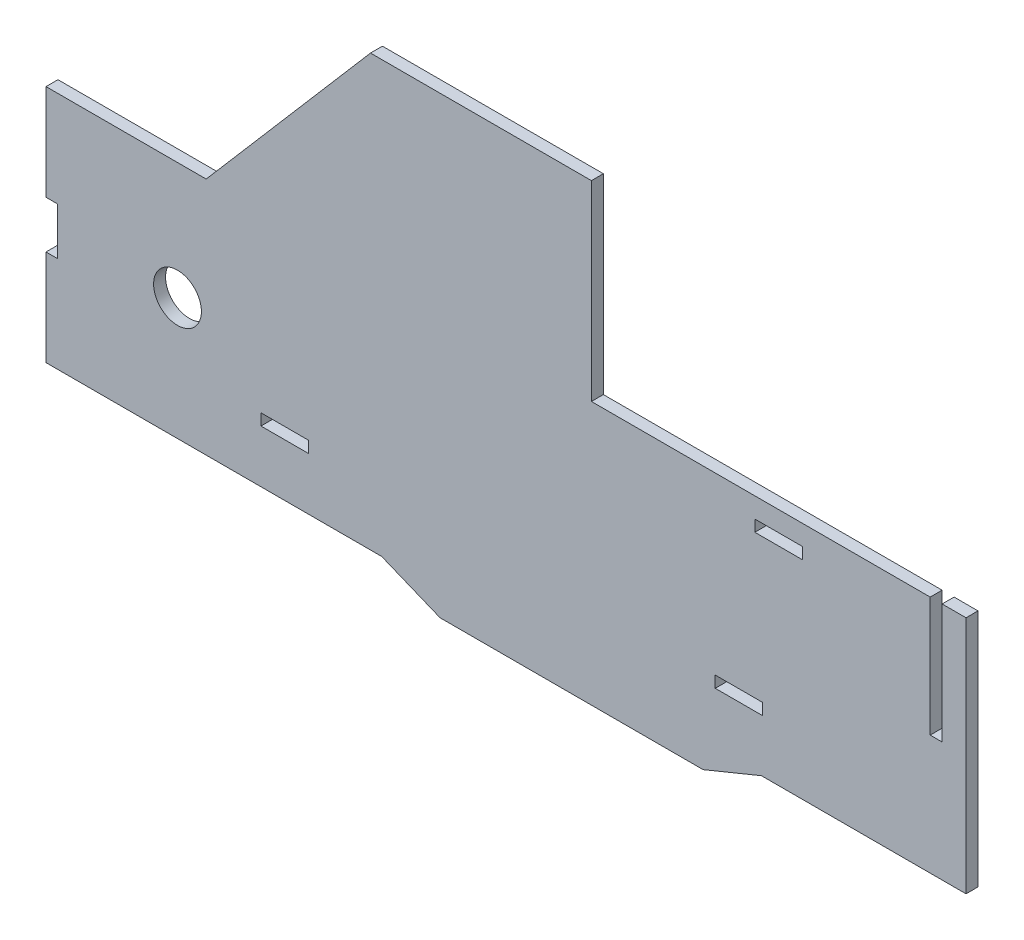
SolidWorks part; units mm, degrees
ref_plane "Front Plane" through (0, 0, 0) normal (0, 0, 1) x (1, 0, 0)
ref_plane "Top Plane" through (0, 0, 0) normal (0, 1, 0) x (1, 0, 0)
ref_plane "Right Plane" through (0, 0, 0) normal (1, 0, 0) x (0, 0, -1)
sketch "Sketch1" plane through (0, 0, 0) normal (0, 0, 1) x (1, 0, 0)
  line L0 (62.1239, 6.35) -> (131.9663, 6.35)
  line L1 (201.8088, 12.7) -> (201.8088, 76.2)
  line L2 (201.8088, 76.2) -> (102.3141, 76.2)
  line L3 (102.3141, 76.2) -> (102.3141, 127)
  line L4 (102.3141, 127) -> (43.6394, 127)
  line L5 (43.6394, 127) -> (0, 76.2)
  line L6 (0, 76.2) -> (-42.5392, 76.2)
  line L7 (-42.5392, 76.2) -> (-42.5392, 12.7)
  line L9 (-42.5392, 12.7) -> (46.6174, 12.7)
  line L10 (46.6174, 12.7) -> (62.1239, 6.35)
  line L11 (201.8088, 12.7) -> (147.4729, 12.7)
  line L12 (147.4729, 12.7) -> (131.9663, 6.35)
  dimension "D1" = 244.348
  dimension "D2" = 6.35
  dimension "D3" = 50.8
  dimension "D4" = 63.5
  dimension "D5" = 99.4947
  dimension "D6" = 16.7564
  dimension "D7" = 16.7564
extrude "Main Side" add sketch "Sketch1" along normal blind 3.175
sketch "Sketch2" plane through (0, 0, 3.175) normal (0, 0, 1) x (1, 0, 0)
  line L0 (-39.4912, 76.2) -> (-39.4912, 12.7) construction
  line L15 (0, 76.2) -> (-42.5392, 76.2) construction
  line L16 (-42.5392, 76.2) -> (-42.5392, 12.7) construction
  line L26 (-39.4912, 18.5744) -> (201.8088, 18.5744) construction
  line L27 (201.8088, 12.7) -> (201.8088, 76.2) construction
  line L28 (81.1588, 18.5744) -> (81.1588, 127) construction
  line L29 (102.3141, 127) -> (43.6394, 127) construction
  line L30 (81.1588, 36.7006) -> (201.8088, 36.7006) construction
  line L41 (62.1239, 6.35) -> (131.9663, 6.35) construction
  line L42 (135.1973, 29.718) -> (147.7703, 29.718)
  line L43 (135.1973, 29.718) -> (135.1973, 26.67)
  line L44 (135.1973, 26.67) -> (147.7703, 26.67)
  line L45 (147.7703, 29.718) -> (147.7703, 26.67)
  line L46 (14.5473, 29.718) -> (14.5473, 26.67)
  line L47 (27.1203, 26.67) -> (14.5473, 26.67)
  line L48 (27.1203, 29.718) -> (27.1203, 26.67)
  line L49 (27.1203, 29.718) -> (14.5473, 29.718)
  line L51 (-42.5392, 12.7) -> (46.6174, 12.7) construction
  point P20 (141.4838, 29.718)
  point P21 (141.4838, 36.7006)
  dimension "D1" = 12.573
  dimension "D2" = 3.048
  dimension "D3" = 20.32
  dimension "D4" = 3.048
extrude "Bottom Plate Holes" cut sketch "Sketch2" against normal through all
sketch "Sketch3" plane through (0, 0, 3.175) normal (0, 0, 1) x (1, 0, 0)
  line L1 (145.7115, 70.866) -> (158.4115, 70.866)
  line L2 (145.7115, 70.866) -> (145.7115, 67.818)
  line L3 (145.7115, 67.818) -> (158.4115, 67.818)
  line L4 (158.4115, 70.866) -> (158.4115, 67.818)
  line L6 (147.7703, 29.718) -> (135.1973, 29.718) construction
  line L7 (201.8088, 76.2) -> (102.3141, 76.2) construction
  point P8 (152.0615, 76.2)
  point P9 (152.0615, 70.866)
  dimension "D1" = 12.7
  dimension "D2" = 3.048
  dimension "D3" = 38.1
extrude "Cut-Extrude1" cut sketch "Sketch3" against normal through all
sketch "Sketch4" plane through (0, 0, 3.175) normal (0, 0, 1) x (1, 0, 0)
  line L0 (-42.5392, 76.2) -> (-42.5392, 12.7) construction
  line L1 (-42.5392, 50.7365) -> (-39.4912, 50.7365)
  line L2 (-42.5392, 50.7365) -> (-42.5392, 38.1635)
  line L3 (-42.5392, 38.1635) -> (-39.4912, 38.1635)
  line L4 (-39.4912, 50.7365) -> (-39.4912, 38.1635)
  point P6 (-42.5392, 44.45)
  point P7 (-42.5392, 44.45)
  dimension "D1" = 3.048
  dimension "D2" = 12.573
extrude "Cut-Extrude2" cut sketch "Sketch4" against normal through all
sketch "Sketch5" plane through (0, 0, 3.175) normal (0, 0, 1) x (1, 0, 0)
  line L0 (201.8088, 76.2) -> (102.3141, 76.2) construction
  line L1 (192.2838, 76.2) -> (195.4588, 76.2)
  line L2 (192.2838, 76.2) -> (192.2838, 44.45)
  line L3 (192.2838, 44.45) -> (195.4588, 44.45)
  line L4 (195.4588, 76.2) -> (195.4588, 44.45)
  line L5 (201.8088, 12.7) -> (201.8088, 76.2) construction
  dimension "D1" = 3.175
  dimension "D2" = 31.75
  dimension "D3" = 6.35
extrude "Cut-Extrude3" cut sketch "Sketch5" against normal through all
sketch "Sketch6" plane through (0, 0, 3.175) normal (0, 0, 1) x (1, 0, 0)
  line L0 (-42.5392, 76.2) -> (-42.5392, 50.7365) construction
  line L1 (0, 76.2) -> (-42.5392, 76.2) construction
  circle A0 centre (-7.6142, 45.085) radius 6.35
  point P4 (0, 0)
  point P6 (-9.0685, 54.271)
  dimension "D2" = 31.115
  dimension "D3" = 12.7
  dimension "D1" = 34.925
extrude "Cut-Extrude4" cut sketch "Sketch6" against normal through all
